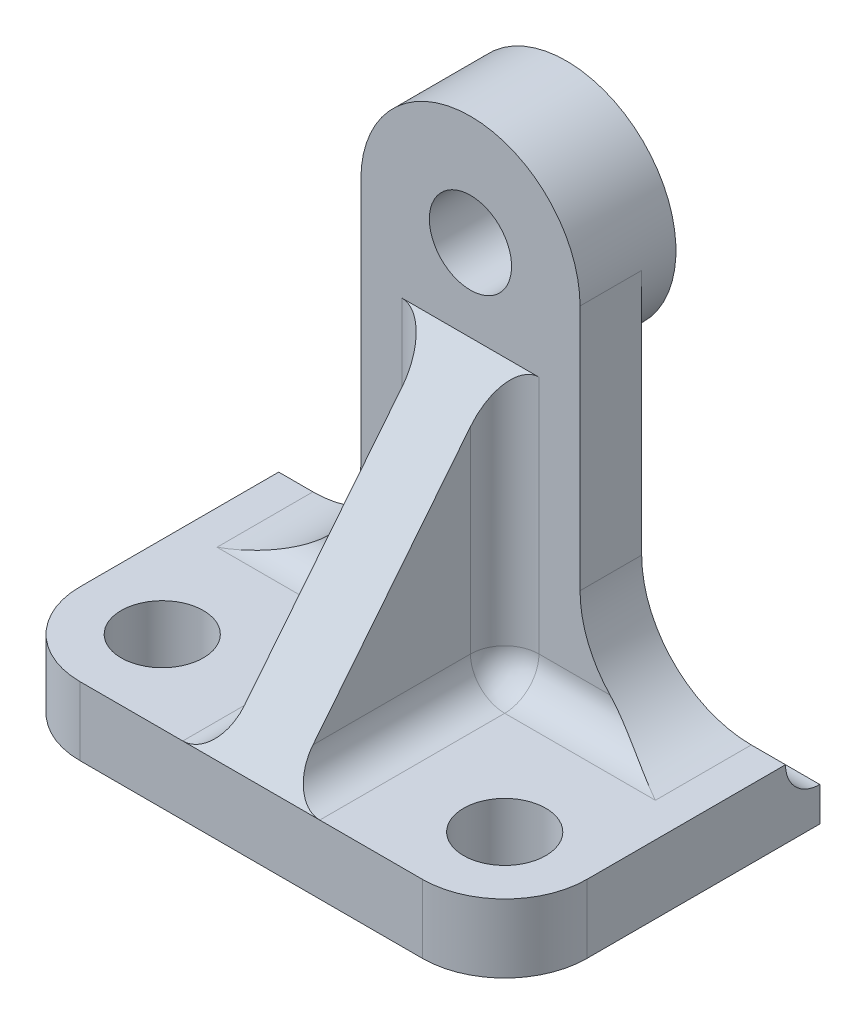
SolidWorks part; units mm, degrees
material "Gray Cast Iron"
ref_plane "Front Plane" through (0, 0, 0) normal (0, 0, 1) x (1, 0, 0)
ref_plane "Top Plane" through (0, 0, 0) normal (0, 1, 0) x (1, 0, 0)
ref_plane "Right Plane" through (0, 0, 0) normal (1, 0, 0) x (0, 0, -1)
sketch "Sketch8" plane through (0, 0, 0) normal (0, 0, 1) x (1, 0, 0)
  line L1 (-32.7822, 0) -> (41.2178, 0)
  line L2 (-32.7822, 0) -> (-32.7822, -10)
  line L3 (-32.7822, -10) -> (41.2178, -10)
  line L4 (41.2178, 0) -> (41.2178, -10)
  dimension "D1" = 74
  dimension "D2" = 10
extrude "Boss-Extrude9" add sketch "Sketch8" along normal blind 46 contours L1 L4 L3 L2
fillet "Fillet8" radius 12 1 edges at (-32.7822, -5, 46)
fillet "Fillet9" radius 12 1 edges at (41.2178, -5, 46)
sketch "Sketch10" plane through (-32.7822, 0, 0) normal (-1, 0, 0) x (0, 0, 1)
  line L0 (34, 0) -> (0, 0) construction
  line L1 (0, 0) -> (0, -10) construction
  arc A0 (5, 0) -> (0, -5) centre (0, 0) cw
  dimension "D1" = 5
extrude "Cut-Extrude3" cut sketch "Sketch10" against normal through all and the other way through all flip side to cut
ref_plane "Plane2" through (4.2178, 0, 0) normal (-1, 0, 0) x (0, 0, 1)
sketch "Sketch13" plane through (0, 0, 0) normal (0, 0, 1) x (1, 0, 0)
  line L1 (-32.7822, 0) -> (41.2178, 0) construction
  line L2 (-11.7822, 0) -> (20.2178, 0)
  line L3 (-11.7822, 0) -> (-11.7822, 52)
  line L5 (20.2178, 0) -> (20.2178, 52)
  line L6 (4.2178, 46.9442) -> (4.2178, -46.9442) construction
  arc A0 (-11.7822, 52) -> (20.2178, 52) centre (4.2178, 52) cw
  circle A1 centre (4.2178, 52) radius 6
  dimension "D2" = 16
  dimension "D3" = 12
  dimension "D1" = 52
extrude "Boss-Extrude10" add sketch "Sketch13" along normal blind 14
sketch "Sketch15" plane through (-11.7822, 0, 0) normal (-1, 0, 0) x (0, 0, 1)
  line L0 (0, 52) -> (0, 0) construction
  line L1 (0, 52) -> (5, 52)
  line L2 (0, 52) -> (0, 0)
  line L3 (0, 0) -> (5, 0)
  line L4 (5, 52) -> (5, 0)
  line L5 (14, 52) -> (0, 52) construction
extrude "Cut-Extrude4" cut sketch "Sketch15" against normal up to next
sketch "Sketch26" plane through (0, 0, 0) normal (0, 0, -1) x (-1, 0, 0)
  circle A0 centre (-4.2178, 52) radius 16
extrude "Boss-Extrude11" add sketch "Sketch26" against normal blind 14
sketch "Sketch27" plane through (0, 0, 0) normal (0, 0, -1) x (-1, 0, 0)
  line L0 (-4.2178, 68) -> (-4.2178, 36) construction
  line L1 (-20.2178, 52) -> (11.7822, 52) construction
  circle A3 centre (-4.2178, 52) radius 16 construction
fillet "Fillet11" radius 5 1 edges at (4.2178, 0, 14)
fillet "Fillet12" radius 16 2 edges at (-11.7822, 0, 12) (20.2178, 0, 12)
sketch "Sketch28" plane through (0, 0, 0) normal (0, 0, -1) x (-1, 0, 0)
  line L0 (-4.2178, 68) -> (-4.2178, 36) construction
  circle A0 centre (-4.2178, 52) radius 6
  dimension "D1" = 12
extrude "Cut-Extrude5" cut sketch "Sketch28" against normal through all
sketch "Sketch31" plane through (4.2178, 0, 0) normal (-1, 0, 0) x (0, 0, 1)
  line L0 (14, 40) -> (46, 0)
  line L2 (19, 0) -> (5, 0) construction
  dimension "D1" = 40
rib "Rib2" sketch "Sketch31" sketch "Sketch31" thickness 10 extrusion direction parallel to sketch draft on no parameters "D1"=10
fillet "Fillet13" radius 5 6 edges at (9.2178, 22.5, 14) (9.2178, 1.4645, 15.4645) (-0.7822, 22.5, 14) (-0.7822, 1.4645, 15.4645) (9.2178, 0, 32.5) (-0.7822, 0, 32.5)
sketch "Sketch36" plane through (0, 0, 0) normal (0, 1, 0) x (1, 0, 0)
  line L0 (-20.7822, -34) -> (29.2178, -34) construction
  line L1 (-20.7822, -19.8724) -> (-20.7822, -51.3013) construction
  line L2 (29.2178, -19) -> (29.2178, -60.5263) construction
  line L3 (36.2178, -19) -> (14.2178, -19) construction
  circle A0 centre (-20.7822, -34) radius 6
  circle A1 centre (29.2178, -34) radius 6
  arc A4 (-32.7822, -34) -> (-20.7822, -46) centre (-20.7822, -34) ccw construction
  arc A6 (29.2178, -46) -> (41.2178, -34) centre (29.2178, -34) ccw construction
  point P14 (-29.2675, -42.4853)
  point P19 (37.7031, -42.4853)
  dimension "D2" = 12
  dimension "D3" = 12
  dimension "D4" = 12
  dimension "D1" = 12
  dimension "D5" = 50
  dimension "D6" = 50
extrude "Cut-Extrude6" cut sketch "Sketch36" against normal through all
